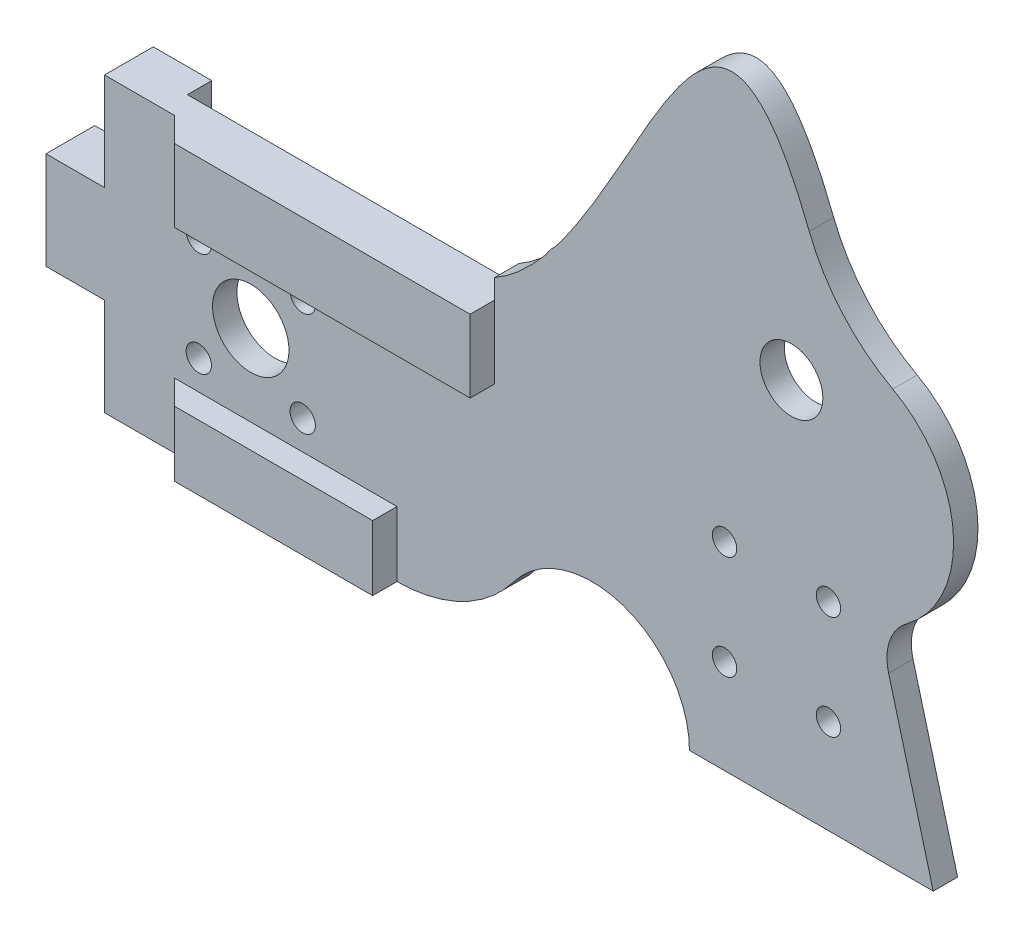
SolidWorks part; units mm, degrees
ref_plane "Front Plane" through (0, 0, 0) normal (0, 0, 1) x (1, 0, 0)
ref_plane "Top Plane" through (0, 0, 0) normal (0, 1, 0) x (1, 0, 0)
ref_plane "Right Plane" through (0, 0, 0) normal (1, 0, 0) x (0, 0, -1)
sketch "Sketch1" plane through (0, 0, 0) normal (0, 0, 1) x (1, 0, 0)
  line L0 (0, 0) -> (107.95, 0)
  line L3 (0, 38.1) -> (0, 25.4)
  line L4 (95.3675, 55.88) -> (0, 38.1)
  line L5 (0, 19.05) -> (100.2273, 19.05) construction
  line L6 (19.05, 19.05) -> (19.05, 28.62) construction
  line L7 (19.05, 19.05) -> (25.817, 25.817) construction
  line L8 (107.95, 0) -> (100.9363, 26.1756)
  line L10 (0, 12.7) -> (0, 0)
  line L11 (0, 25.4) -> (-7.62, 25.4)
  line L13 (0, 12.7) -> (-7.62, 12.7)
  line L14 (-7.62, 25.4) -> (-7.62, 12.7)
  line L15 (100.9363, 26.1756) -> (100.8688, 26.4276)
  arc A0 (100.8688, 26.4276) -> (95.3675, 55.88) centre (95.3675, 40.64) ccw
  circle A1 centre (95.3675, 40.64) radius 4.0957 construction
  circle A2 centre (19.05, 19.05) radius 9.57 construction
  circle A3 centre (25.817, 25.817) radius 1.651
  circle A4 centre (25.817, 12.283) radius 1.651
  circle A5 centre (12.283, 12.283) radius 1.651
  circle A6 centre (12.283, 25.817) radius 1.651
  point P26 (19.05, 19.05)
  dimension "D1" = 8.1915
  dimension "D5" = 15.24
  dimension "D4" = 19.14
  dimension "D7" = 3.302
  dimension "D11" = 97.0107
  dimension "D2" = 38.1
  dimension "D3" = 40.64
  dimension "D6" = 107.95
  dimension "D8" = 45
  dimension "D9" = 4
  dimension "D10" = 19.05
  dimension "D12" = 75
  dimension "D14" = 12.7
  dimension "D15" = 12.7
  dimension "D16" = 7.62
extrude "Boss-Extrude1" add sketch "Sketch1" along normal blind 3.175
sketch "Sketch2" plane through (0, 0, 3.175) normal (0, 0, 1) x (1, 0, 0)
  circle A0 centre (95.3675, 40.64) radius 38.1 construction
sketch "Sketch6" plane through (0, 0, 3.175) normal (0, 0, 1) x (1, 0, 0)
  line L0 (0, 0) -> (107.95, 0) construction
  line L1 (50.8, 0) -> (76.2, 0)
  arc A0 (76.2, 0) -> (50.8, 0) centre (63.5, 0) ccw
  dimension "D1" = 25.4
  dimension "D2" = 31.75
extrude "Cut-Extrude2" cut sketch "Sketch6" against normal blind 6.35
sketch "Sketch7" plane through (0, 0, 3.175) normal (0, 0, 1) x (1, 0, 0)
  line L0 (12.283, 25.817) -> (25.817, 12.283) construction
  line L1 (12.283, 12.283) -> (25.817, 25.817) construction
  line L2 (12.283, 25.817) -> (78.4839, 25.817) construction
  line L3 (11.7326, 12.283) -> (12.283, 12.283) construction
  circle A0 centre (19.05, 19.05) radius 4.9784
  circle A4 centre (80.7666, 12.283) radius 1.5875
  circle A5 centre (94.2997, 12.283) radius 1.5875
  circle A6 centre (80.7666, 25.817) radius 1.5875
  circle A7 centre (94.2997, 25.817) radius 1.5875
  dimension "D1" = 9.9568
  dimension "D2" = 3.175
  dimension "D3" = 13.5331
extrude "Cut-Extrude3" cut sketch "Sketch7" against normal through all
fillet "Fillet1" radius 6.35 1 edges at (100.8688, 26.4276, 1.5875)
sketch "Sketch8" plane through (0, 0, 3.175) normal (0, 0, 1) x (1, 0, 0)
  line L1 (0, 38.1) -> (50.8, 38.1)
  line L2 (0, 38.1) -> (0, 50.8)
  line L3 (0, 50.8) -> (50.8, 50.8)
  line L4 (50.8, 38.1) -> (50.8, 50.8)
  dimension "D1" = 50.8
  dimension "D2" = 12.7
extrude "Cut-Extrude4" cut sketch "Sketch8" against normal blind 50.8
sketch "Sketch9" plane through (0, 0, 3.175) normal (0, 0, 1) x (1, 0, 0)
  line L3 (50.8, 40.64) -> (57.15, 40.64)
  line L5 (57.15, 40.64) -> (50.8, 40.64)
  line L6 (57.15, 40.64) -> (57.15, 50.8)
  line L7 (57.15, 50.8) -> (50.8, 50.8)
  line L8 (50.8, 40.64) -> (50.8, 50.8)
  line L9 (0, 38.1) -> (50.8, 38.1) construction
  line M8 (50.8, 47.571) -> (50.8, 38.1)
  line M21 (95.3675, 55.88) -> (50.8, 47.571)
  dimension "D1" = 10.16
  dimension "D2" = 2.54
  dimension "D3" = 6.35
extrude "Cut-Extrude5" cut sketch "Sketch9" against normal blind 19.304 contours L3 L6 M21 M8 region at (54.0583, 44.4092, 3.175)
fillet "Fillet6" radius 6.35 1 edges at (57.15, 40.64, 1.5875)
fillet "Fillet7" radius 6.35 1 edges at (57.15, 48.7549, 1.5875)
fillet "Fillet8" radius 19.05 1 edges at (50.8, 0, 1.5875)
sketch "Sketch12" plane through (0, 0, 3.175) normal (0, 0, 1) x (1, 0, 0)
  line L0 (107.95, 0) -> (146.812, 0) construction
  line L1 (8.0257, 45.4128) -> (80.6683, 75.7903) construction
  line L2 (95.3675, 40.64) -> (80.6683, 75.7903) construction
  line L3 (80.6683, 75.7903) -> (79.4434, 78.7195) construction
  line L4 (50.8, 40.64) -> (85.0271, 40.64)
  line L5 (85.0271, 40.64) -> (95.3675, 55.88)
  arc A0 (61.8128, 49.6242) -> (56.8883, 45.1859) centre (62.9766, 43.3817) ccw construction
  circle A1 centre (19.05, 19.05) radius 28.575 construction
  circle A2 centre (95.3675, 40.64) radius 38.1 construction
  circle A3 centre (80.6683, 75.7903) radius 3.175 construction
  spline S0 degree 3 poles (50.8, 40.64) (70.7778, 52.1788) (78.5943, 111.5434) (95.3675, 55.88) knots 0 0 0 0 1 1 1 1
  dimension "D2" = 6.35
  dimension "D1" = 38.862
extrude "Boss-Extrude2" add sketch "Sketch12" against normal blind 3.175
fillet "Fillet9" radius 24.13 1 edges at (95.3675, 55.88, 1.5875)
sketch "Sketch13" plane through (0, 0, 0) normal (0, 0, -1) x (-1, 0, 0)
  line L1 (-50.8, 38.1) -> (-9.1321, 38.1)
  line L2 (-50.8, 38.1) -> (-50.8, 28.6404)
  line L3 (-50.8, 28.6404) -> (-9.1321, 28.6404)
  line L6 (-9.1321, 8.4682) -> (-38.1, 8.4682)
  line L7 (-9.1321, 8.4682) -> (-9.1321, 0)
  line L8 (-9.1321, 0) -> (-38.1, 0)
  line L9 (-38.1, 8.4682) -> (-38.1, 0)
  line L10 (-9.1321, 38.1) -> (-9.1321, 28.6404)
extrude "Boss-Extrude3" add sketch "Sketch13" against normal blind 6.35
sketch "Sketch16" plane through (0, 0, 3.175) normal (0, 0, 1) x (1, 0, 0)
  circle A0 centre (89.4737, 48.423) radius 4.0958
  circle A1 centre (94.2997, 25.817) radius 1.5875 construction
  dimension "D1" = 22.606
  dimension "D2" = 4.826
extrude "Cut-Extrude8" cut sketch "Sketch16" against normal through all
sketch "Sketch18" plane through (0, 0, 3.175) normal (0, 0, 1) x (1, 0, 0)
  line L0 (0, 0) -> (7.62, 0)
  line L1 (0, 0) -> (9.1321, 0) construction
  line L2 (7.62, 0) -> (7.62, 38.1)
  line L3 (0, 38.1) -> (9.1321, 38.1) construction
  line L4 (7.62, 38.1) -> (0, 38.1)
  line L5 (0, 38.1) -> (0, 25.4)
  line L6 (0, 25.4) -> (-7.62, 25.4)
  line L7 (-7.62, 25.4) -> (-7.62, 12.7)
  line L8 (-7.62, 12.7) -> (0, 12.7)
  line L9 (0, 12.7) -> (0, 0)
  dimension "D1" = 7.62
extrude "Boss-Extrude4" add sketch "Sketch18" against normal blind 6.35
sketch "Sketch19" plane through (0, 38.1, 0) normal (0, 1, 0) x (1, 0, 0)
  line L0 (9.1321, -3.175) -> (12.3071, -6.35)
  line L1 (9.1321, -6.35) -> (9.1321, -3.175) construction
  line L2 (0, -3.175) -> (9.1321, -3.175) construction
  line L3 (9.1321, -6.35) -> (50.8, -6.35) construction
  line L4 (12.3071, -6.35) -> (9.1321, -6.35)
  line L5 (9.1321, -6.35) -> (9.1321, -3.175)
  dimension "D1" = 45
extrude "Cut-Extrude9" cut sketch "Sketch19" against normal through all
